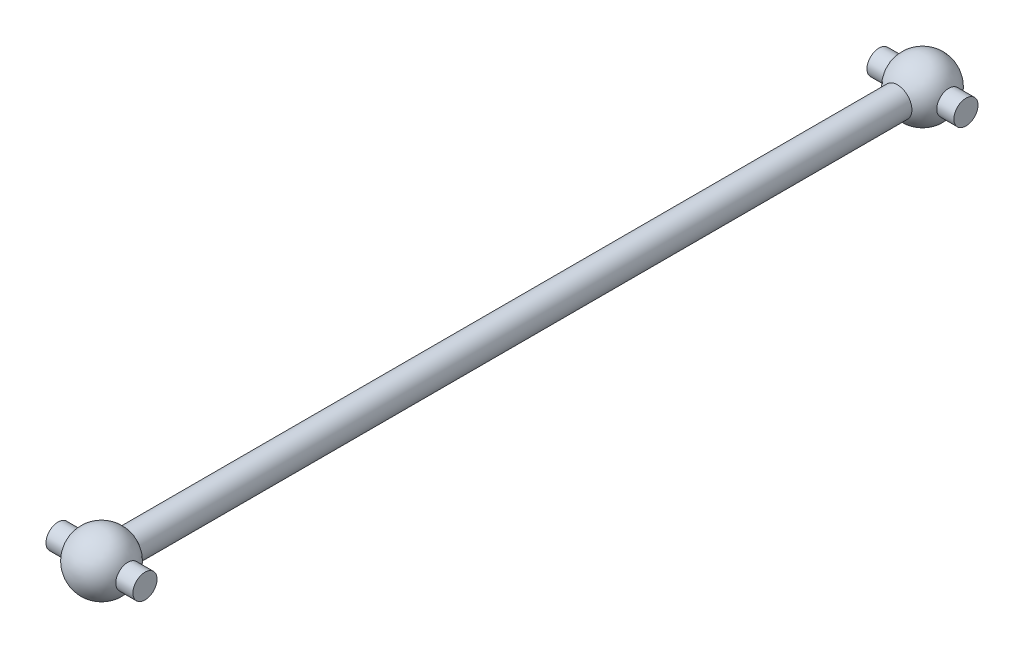
SolidWorks part; units mm, degrees
ref_plane "Front Plane" through (0, 0, 0) normal (0, 0, 1) x (1, 0, 0)
ref_plane "Top Plane" through (0, 0, 0) normal (0, 1, 0) x (1, 0, 0)
ref_plane "Right Plane" through (0, 0, 0) normal (1, 0, 0) x (0, 0, -1)
sketch "Sketch1" plane through (0, 0, 0) normal (0, 0, 1) x (1, 0, 0)
  circle A0 centre (0, 0) radius 1.5
  dimension "D1" = 3
extrude "Boss-Extrude1" add sketch "Sketch1" along normal blind 42.5 and the other way blind 42.5
sketch "Sketch2" plane through (0, 0, 0) normal (1, 0, 0) x (0, 0, -1)
  line L0 (-42.5, 1.5) -> (-42.5, -1.5) construction
  line L1 (-42.5, 3) -> (-42.5, -3)
  circle A0 centre (-42.5, 0) radius 3
  dimension "D1" = 6
revolve "Revolve1" add sketch "Sketch2" angle 360 about L1 region at (0, 0, 43.7732)
sketch "Sketch3" plane through (0, 0, 0) normal (1, 0, 0) x (0, 0, -1)
  circle A0 centre (-42.5, 0) radius 1.25
  arc A1 (-39.9019, 1.5) -> (-39.9019, -1.5) centre (-42.5, 0) ccw construction
  dimension "D1" = 2.5
extrude "Boss-Extrude2" add sketch "Sketch3" along normal blind 4.5 and the other way blind 4.5
mirror "Mirror1" about plane through (0, 0, 0) normal (0, 0, 1) of "Boss-Extrude2", "Revolve1"
ref_point "Point1"
ref_point "Point2"
